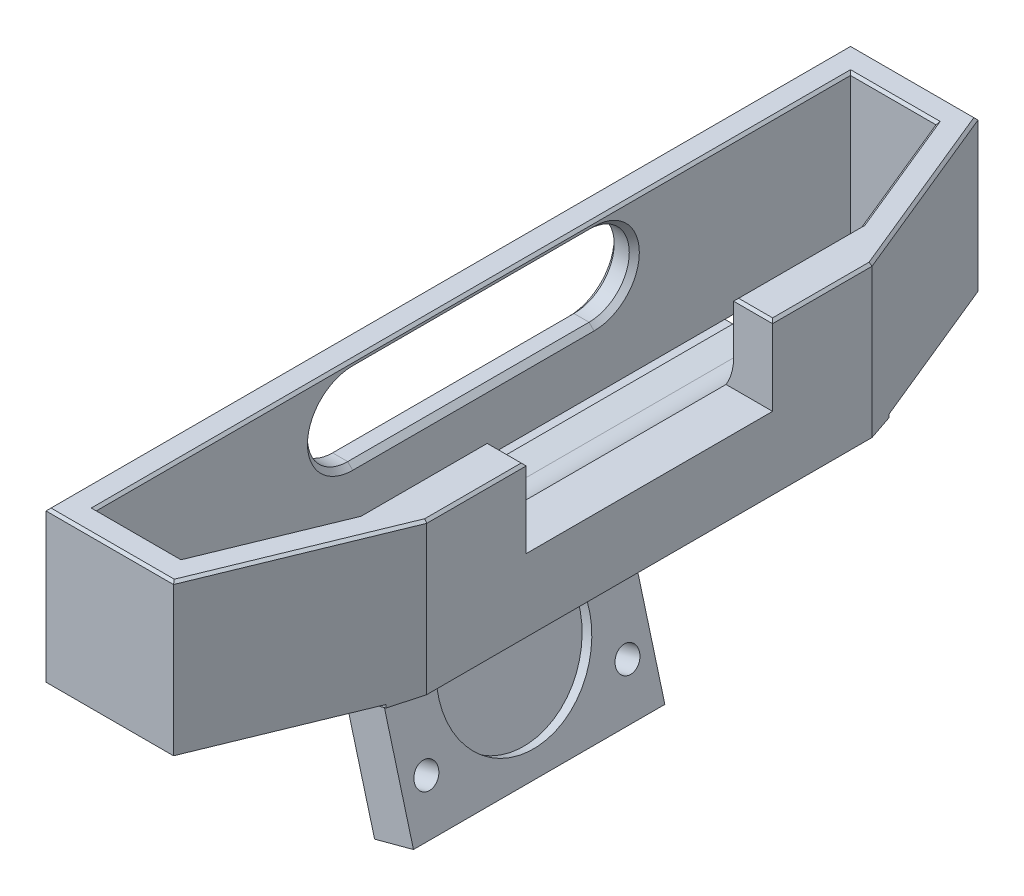
SolidWorks part; units mm, degrees
ref_plane "Ebene vorne" through (0, 0, 0) normal (0, 0, 1) x (1, 0, 0)
ref_plane "Ebene oben" through (0, 0, 0) normal (0, 1, 0) x (1, 0, 0)
ref_plane "Ebene rechts" through (0, 0, 0) normal (1, 0, 0) x (0, 0, -1)
sketch "Skizze1" plane through (0, 0, 0) normal (0, 0, 1) x (1, 0, 0)
  line L1 (20, -15) -> (-20, -15)
  line L2 (20, -15) -> (20, 15)
  line L3 (20, 15) -> (-20, 15)
  line L4 (-20, -15) -> (-20, 15)
  line L5 (20, -15) -> (-20, 15) construction
  line L6 (20, 15) -> (-20, -15) construction
  point P0 (0, 0)
  point P6 (-20, 0)
  point P7 (20, 0)
  dimension "D1" = 30
  dimension "D2" = 40
extrude "Aufsatz-Linear austragen1" add sketch "Skizze1" along normal blind 160
sketch "Skizze2" plane through (0, 15, 0) normal (0, 1, 0) x (1, 0, 0)
  line L0 (-20, -160) -> (-20, 0) construction
  line L1 (-15, -5) -> (-5, -5)
  line L2 (-15, -5) -> (-15, -155)
  line L3 (-15, -155) -> (-5, -155)
  line L4 (-5, -5) -> (-5, -155)
  line L5 (20, -160) -> (-20, -160) construction
  dimension "D1" = 5
  dimension "D2" = 150
  dimension "D3" = 10
  dimension "D4" = 5
extrude "Schnitt-Linear austragen1" cut sketch "Skizze2" against normal through all
sketch "Skizze3" plane through (0, 0, 160) normal (0, 0, 1) x (1, 0, 0)
  line L0 (20, 15) -> (-20, 15) construction
  line L1 (-20, 15) -> (-20, -15) construction
  line L2 (-5, -15) -> (-5, -6.6)
  line L3 (-20, -15) -> (20, -15) construction
  line L4 (-5, -15) -> (-15, -15)
  line L5 (-15, -15) -> (-15, 15)
  line L6 (-15, 15) -> (-3, 15)
  line L7 (-5, -6.6) -> (2, -5.5)
  line L8 (12.25, 4.75) -> (12.25, 15)
  line L9 (12.25, 15) -> (-3, 15)
  arc A0 (2, -5.5) -> (12.25, 4.75) centre (2, 4.75) ccw
  dimension "D1" = 10.25
  dimension "D2" = 17
  dimension "D3" = 8.4
  dimension "D4" = 5
  dimension "D5" = 10
  dimension "D6" = 10.25
extrude "Schnitt-Linear austragen2" cut sketch "Skizze3" against normal offset from surface (100 mm away) 30 from offset 30 up to face at (0, 0, 0) offset against normal yes
sketch "Skizze4" plane through (0, 15, 0) normal (0, 1, 0) x (1, 0, 0)
  line L0 (12.25, -30) -> (12.25, -130) construction
  line L1 (20, -104.5) -> (12.25, -104.5)
  line L2 (20, -104.5) -> (20, -55.5)
  line L3 (20, -55.5) -> (12.25, -55.5)
  line L4 (12.25, -104.5) -> (12.25, -55.5)
  line L5 (20, -104.5) -> (12.25, -55.5) construction
  line L6 (20, -55.5) -> (12.25, -104.5) construction
  line L7 (20, 0) -> (-20, 0) construction
  line L8 (20, -160) -> (20, 0) construction
  point P0 (16.125, -80)
  dimension "D1" = 80
  dimension "D2" = 49
  dimension "D3" = 0
extrude "Schnitt-Linear austragen3" cut sketch "Skizze4" against normal blind 15.6
sketch "Skizze5" plane through (12.25, 0, 0) normal (1, 0, 0) x (0, 0, -1)
  line L1 (-104.5, 4.75) -> (-55.5, 4.75)
  line L2 (-104.5, 4.75) -> (-104.5, -0.6)
  line L3 (-104.5, -0.6) -> (-55.5, -0.6)
  line L4 (-55.5, 4.75) -> (-55.5, -0.6)
extrude "Schnitt-Linear austragen4" cut sketch "Skizze5" against normal blind 5
sketch "Skizze6" plane through (0, 15, 0) normal (0, 1, 0) x (1, 0, 0)
  line L0 (-5, -5) -> (2, -5)
  line L1 (2, -5) -> (12.25, -30)
  line L2 (12.25, -30) -> (-5, -30)
  line L3 (-5, -30) -> (-5, -5)
  dimension "D1" = 17
extrude "Schnitt-Linear austragen5" cut sketch "Skizze6" against normal blind 21
ref_plane "Ebene1" through (0, 0, 80) normal (0, 0, 1) x (1, 0, 0)
mirror "Spiegeln3" about plane through (0, 0, 80) normal (0, 0, 1) of "Schnitt-Linear austragen5"
sketch "Skizze7" plane through (-20, 0, 0) normal (-1, 0, 0) x (0, 0, 1)
  line L0 (56, 5) -> (104, 5) construction
  line L1 (56, 13) -> (104, 13)
  line L2 (56, -3) -> (104, -3)
  line L3 (0, 15) -> (0, -15) construction
  line L4 (160, 15) -> (0, 15) construction
  arc A0 (56, 13) -> (56, -3) centre (56, 5) ccw
  arc A1 (104, -3) -> (104, 13) centre (104, 5) ccw
  point P2 (80, 5)
  dimension "D2" = 8
  dimension "D1" = 48
  dimension "D3" = 80
  dimension "D4" = 10
extrude "Schnitt-Linear austragen6" cut sketch "Skizze7" against normal blind 5
sketch "Sketch1" plane through (0, 0, 160) normal (0, 0, 1) x (1, 0, 0)
  line L0 (-20, -15) -> (-20, -25.718)
  line L1 (-20, -25.718) -> (20, -15)
  line L2 (20, -15) -> (-20, -15)
  dimension "D1" = 15
extrude "Boss-Extrude1" add sketch "Sketch1" against normal blind 100 from offset 30 offset against normal yes
sketch "Sketch2" plane through (0, 0, 160) normal (0, 0, 1) x (1, 0, 0)
  line L0 (-20, -25.718) -> (-9.6472, -64.355)
  line L1 (-9.6472, -64.355) -> (-1.9198, -62.2844)
  line L2 (-1.9198, -62.2844) -> (-12.2726, -23.6474)
  line L3 (-20, -25.718) -> (20, -15) construction
  line L4 (-12.2726, -23.6474) -> (-20, -25.718)
  dimension "D1" = 8
  dimension "D2" = 40
extrude "Boss-Extrude2" add sketch "Sketch2" against normal blind 50 from offset 55 offset against normal yes
sketch "Sketch4" plane through (-25.0897, -6.7228, 0) normal (-0.9659, -0.2588, 0) x (0, 0, 1)
  line L0 (55, -19.6653) -> (105, -19.6653) construction
  line L1 (60, -30.2653) -> (100, -30.2653)
  line L2 (60, -30.2653) -> (60, -50.2653)
  line L3 (60, -50.2653) -> (100, -50.2653)
  line L4 (100, -30.2653) -> (100, -50.2653)
  line L5 (55, -19.6653) -> (55, -59.6653) construction
  dimension "D1" = 40
  dimension "D2" = 20
  dimension "D3" = 30.6
  dimension "D4" = 5
hole_wizard "M4 Clearance Hole1" positions "Sketch5" profile "Sketch6" hole size "M4" standard "DIN" end condition through all
sketch "Sketch5" plane through (-25.0897, -6.7228, 0) normal (-0.9659, -0.2588, 0) x (0, 0, 1)
  point P0 (60, -30.2653)
  point P3 (100, -30.2653)
  point P6 (100, -50.2653)
  point P9 (60, -50.2653)
sketch "Sketch6" plane through (-17.2565, -35.9568, 60) normal (0, 0, 1) x (0.2588, -0.9659, 0)
  line L0 (0, 0) -> (0, 49.1756)
  line L1 (0, 49.1756) -> (2.4, 49.1756)
  line L2 (2.4, 49.1756) -> (2.4, 0)
  line L5 (2.4, 0) -> (0, 0)
  line L11 (0, -6.35) -> (0, 107.95) construction
  dimension "Thru Hole Dia." = 4.8
  dimension "Thru Hole Depth" = 49.1756
sketch "Sketch7" plane through (0, 15, 0) normal (0, 1, 0) x (1, 0, 0)
  line L0 (5.3539, 0) -> (20, -35.7221)
  line L1 (20, 0) -> (-20, 0) construction
  line L2 (20, -55.5) -> (20, 0) construction
  line L3 (20, -35.7221) -> (45.1921, 3.8342)
  line L4 (45.1921, 3.8342) -> (5.3539, 0)
  line L5 (12.25, -30) -> (2, -5) construction
  line L6 (12.25, -30) -> (2, -5) construction
  dimension "D1" = 5
extrude "Cut-Extrude1" cut sketch "Sketch7" against normal through all
mirror "Mirror1" about plane through (0, 0, 80) normal (0, 0, 1) of "Cut-Extrude1"
sketch "Sketch8" plane through (-17.3623, -4.6522, 0) normal (0.9659, 0.2588, 0) x (0, 0, -1)
  circle A0 centre (-80, -40.2653) radius 15
  circle A1 centre (-100, -30.2653) radius 2.4 construction
  circle A2 centre (-100, -50.2653) radius 2.4 construction
  dimension "D1" = 30
  dimension "D2" = 20
  dimension "D3" = 10
extrude "Cut-Extrude2" cut sketch "Sketch8" against normal blind 2
chamfer "Chamfer1" distance 0.5 angle 45 16 edges at (-7.323, 15, 160) (-20, 15, 80) (-7.323, 15, 0) (12.677, 15, 17.8611) (20, 15, 45.6111) (16.125, 15, 55.5) (12.25, 15, 42.75) (7.125, 15, 17.5) (-6.5, 15, 5) (-15, 15, 80) (-6.5, 15, 155) (7.125, 15, 142.5) (12.25, 15, 117.25) (16.125, 15, 104.5) (20, 15, 114.3889) (12.677, 15, 142.1389)
chamfer "Chamfer2" distance 1 angle 45 8 edges at (-15, 5, 112) (-15, 13, 80) (-15, -3, 80) (-15, 5, 48) (-20, 5, 112) (-20, 13, 80) (-20, -3, 80) (-20, 5, 48)
